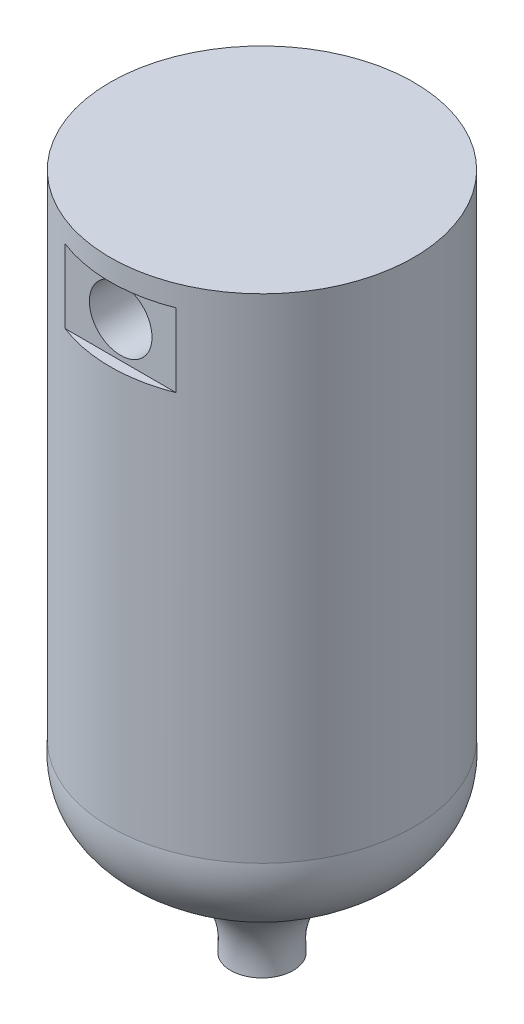
SolidWorks part; units mm, degrees
ref_plane "Front Plane" through (0, 0, 0) normal (0, 0, 1) x (1, 0, 0)
ref_plane "Top Plane" through (0, 0, 0) normal (0, 1, 0) x (1, 0, 0)
ref_plane "Right Plane" through (0, 0, 0) normal (1, 0, 0) x (0, 0, -1)
sketch "Sketch1" plane through (0, 0, 0) normal (0, 0, 1) x (1, 0, 0)
  line L1 (-3.8791, 0) -> (-3.8791, -12)
  line L4 (0, 0) -> (0, -10.1137) construction
  line L6 (-3.8791, 0) -> (0, 0)
  line L7 (-0.8, -17.3166) -> (0, -17.3166)
  line L8 (0, 0) -> (0, -17.3166)
  spline S0 degree 1 poles (-3.8791, -12) (-3.8791, -12.6028) knots 0 0 1 1
  spline S1 degree 3 poles (-3.8791, -12.6028) (-4.0985, -15.2494) (-0.5348, -14.7259) (-0.8, -17.3166) knots 0 0 0 0 1 1 1 1
  dimension "D5" = 0.6028
  dimension "D6" = 6.0222
  dimension "D1" = 0.8
  dimension "D2" = 12
  dimension "D3" = 3.8791
  dimension "D4" = 17.3166
  dimension "D7" = 1
  dimension "D8" = 1.3983
  dimension "D9" = 2.0099
revolve "Revolve1" add sketch "Sketch1" angle 360 about L4
ref_plane "Plane1" through (0, 0, 3.9) normal (0, 0, 1) x (1, 0, 0)
sketch "Sketch3" plane through (0, 0, 3.9) normal (0, 0, 1) x (1, 0, 0)
  circle A0 centre (0, -1.5) radius 0.8
  dimension "D1" = 1.6
  dimension "D2" = 1.5
extrude "Cut-Extrude1" cut sketch "Sketch3" against normal blind 2
ref_plane "Plane2" through (0, 0, -3.9) normal (0, 0, 1) x (1, 0, 0)
sketch "Sketch4" plane through (0, 0, -3.9) normal (0, 0, 1) x (1, 0, 0)
  circle A0 centre (0, -1.5) radius 0.8 construction
  circle A1 centre (0, -1.5) radius 0.8
extrude "Cut-Extrude2" cut sketch "Sketch4" along normal blind 2
sketch "Sketch5" plane through (0, -17.3166, 0) normal (0, -1, 0) x (1, 0, 0)
  point P0 (0, 0)
sketch "Sketch6" plane through (0, 0, 0) normal (1, 0, 0) x (0, 0, -1)
  line L0 (0, 37.9207) -> (0, -47.729) construction
  line L1 (-3.8791, -0.5398) -> (-3.6105, -0.5398)
  line L2 (-3.8791, 0) -> (-3.8791, -0.7001) construction
  line L3 (-3.6105, -0.5398) -> (-3.6105, -2.4162)
  line L4 (-3.6105, -2.4162) -> (-3.8791, -2.4162)
  line L5 (-3.8791, -2.3) -> (-3.8791, -12.6028) construction
  line L6 (-3.8791, -2.4162) -> (-3.8791, -0.5398)
extrude "Cut-Extrude3" cut sketch "Sketch6" against normal blind 5 and the other way blind 5
sketch "Sketch7" plane through (0, 0, 3.6105) normal (0, 0, 1) x (1, 0, 0)
  circle A0 centre (0, -1.5) radius 0.8 construction
  circle A1 centre (0, -1.5) radius 0.8
